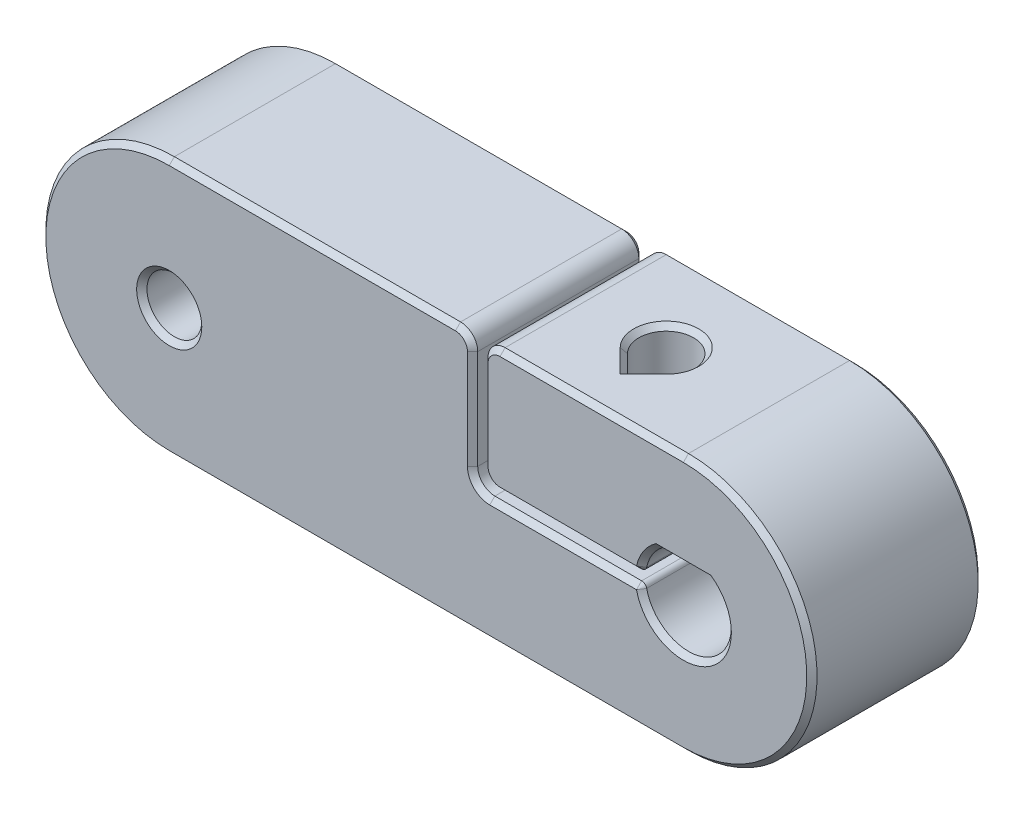
SolidWorks part; units mm, degrees
ref_plane "前视基准面" through (0, 0, 0) normal (0, 0, 1) x (1, 0, 0)
ref_plane "上视基准面" through (0, 0, 0) normal (0, 1, 0) x (1, 0, 0)
ref_plane "右视基准面" through (0, 0, 0) normal (1, 0, 0) x (0, 0, -1)
sketch "草图1" plane through (0, 0, 0) normal (0, 0, 1) x (1, 0, 0)
  line L0 (0, 0) -> (0, 2) construction
  line L1 (1.5, 2) -> (-1.5, 2)
  line L2 (0, 500) -> (0, -500) construction
  line L3 (-500, 0) -> (500, 0) construction
  line L4 (0, -7.5) -> (-30, -7.5)
  line L5 (0, 7.5) -> (-30, 7.5)
  arc A0 (-1.5, 2) -> (1.5, 2) centre (0, 0) ccw
  circle A1 centre (-30, 0) radius 1.6
  arc A2 (-30, 7.5) -> (-30, -7.5) centre (-30, 0) ccw
  arc A3 (0, -7.5) -> (0, 7.5) centre (0, 0) ccw
  dimension "D1" = 5
  dimension "D3" = 30
  dimension "D4" = 3.2
  dimension "D5" = 15
  dimension "D2" = 2
extrude "凸台-拉伸1" add sketch "草图1" along normal mid plane 10
sketch "草图2" plane through (0, 0, 5) normal (0, 0, 1) x (1, 0, 0)
  line L0 (0, 0) -> (-12, 0) construction
  line L1 (-12, 0) -> (-12, 7.5) construction
  line L2 (0, 7.5) -> (-30, 7.5) construction
  line L3 (0, 0.3) -> (-11.7, 0.3)
  line L4 (-11.7, 0.3) -> (-11.7, 7.5)
  line L5 (0, -0.3) -> (-12.3, -0.3)
  line L6 (-12.3, -0.3) -> (-12.3, 7.5)
  line L7 (-11.7, 7.5) -> (-12.3, 7.5)
  line L8 (0, 0.3) -> (0, -0.3)
  dimension "D1" = 12
  dimension "D2" = 0.3
  dimension "D3" = 0.3
extrude "切除-拉伸1" cut sketch "草图2" against normal through all
sketch "草图3" plane through (0, 7.5, 0) normal (0, 1, 0) x (1, 0, 0)
  line L0 (-6, 5) -> (-6, -5) construction
  line L1 (0, 5) -> (-11.7, 5) construction
  line L2 (0, -5) -> (-11.7, -5) construction
  line L3 (0, 0) -> (-46.0212, 0) construction
  line L6 (-7.1314, -1.1314) -> (-6, -2.2627)
  line L7 (-4.8686, -1.1314) -> (-6, -2.2627)
  arc A1 (-7.1314, -1.1314) -> (-4.8686, -1.1314) centre (-6, 0) cw
  point P6 (-6, 0)
  point P7 (-6, 0)
  dimension "D2" = 1.6
  dimension "D1" = 6
  dimension "D5" = 45
extrude "切除-拉伸2" cut sketch "草图3" against normal blind 7.5
sketch "草图4" plane through (0, -0.3, 0) normal (0, 1, 0) x (1, 0, 0)
  line L3 (-6, 0) -> (-6, -1.8385) construction
  line L4 (-6, -1.8385) -> (-6.9192, -0.9192)
  line L5 (-6, -1.8385) -> (-5.0808, -0.9192)
  circle A0 centre (-6, 0) radius 1.6 construction
  circle A2 centre (-6, 0) radius 1.6 construction
  arc A5 (-5.0808, -0.9192) -> (-6.9192, -0.9192) centre (-6, 0) ccw
  dimension "D3" = 45
extrude "切除-拉伸3" cut sketch "草图4" against normal blind 18.5
fillet "圆角1" radius 1 4 edges at (-12.3, -0.3, 0) (-12.3, 7.5, 0) (-11.7, 7.5, 0) (-11.7, 0.3, 0)
fillet "圆角2" radius 0.3 2 edges at (-2.4819, -0.3, 0) (-2.4819, 0.3, 0)
chamfer "倒角1" distance 0.3 angle 45 50 edges at (-28.4, 0, -5) (-12.0071, -0.0071, -5) (-12.3, 3.6, -5) (-12.5929, 7.2071, -5) (-21.65, 7.5, -5) (-37.5, 0, -5) (-15, -7.5, -5) (7.5, 0, -5) (-5.35, 7.5, -5) (-11.4071, 7.2071, -5) (-11.7, 3.9, -5) (-11.4071, 0.5929, -5) (-6.7175, 0.3, -5) (-2.5469, 0.3662, -5) (-2.1026, 1.3525, -5) (0, 2, -5) (1.3525, -2.1026, -5) (-2.5469, -0.3662, -5) (-7.0175, -0.3, -5) (-28.4, 0, 5) (0, 2, 5) (-2.1026, 1.3525, 5) (-2.5469, 0.3662, 5) (-6.7175, 0.3, 5) (-11.4071, 0.5929, 5) (-11.7, 3.9, 5) (-11.4071, 7.2071, 5) (-5.35, 7.5, 5) (7.5, 0, 5) (-15, -7.5, 5) (-37.5, 0, 5) (-21.65, 7.5, 5) (-12.5929, 7.2071, 5) (-12.3, 3.6, 5) (-12.0071, -0.0071, 5) (-7.0175, -0.3, 5) (-2.5469, -0.3662, 5) (1.3525, -2.1026, 5) (-5.5404, -7.5, 1.3789) (-6.4596, -7.5, 1.3789) (-6, -7.5, -1.3) (-5.5404, -0.3, 1.3789) (-6.4596, -0.3, 1.3789) (-6, -0.3, -1.3) (-5.4343, 0.3, 1.6971) (-6.5657, 0.3, 1.6971) (-6, 0.3, -1.6) (-5.4343, 7.5, 1.6971) (-6.5657, 7.5, 1.6971) (-6, 7.5, -1.6)
